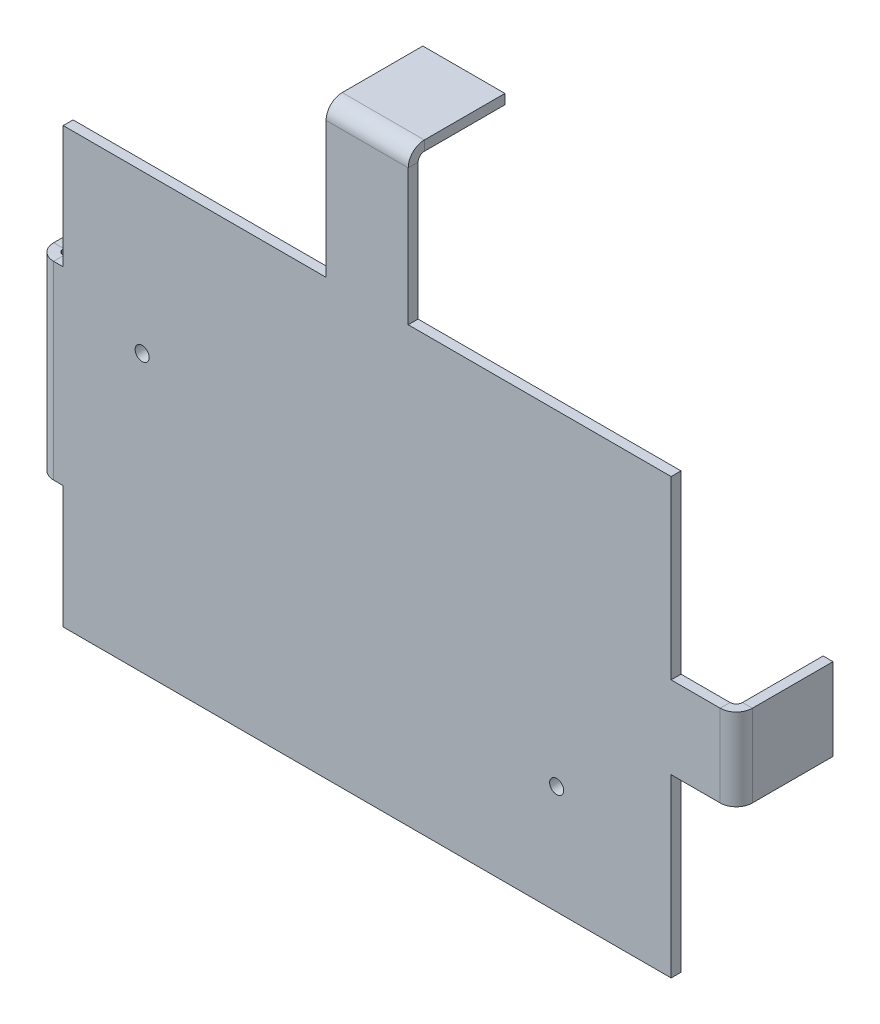
SolidWorks part; units mm, degrees
note: The reader was unsure of these and kept them because the rebuilt part matched: flange length of "Edge-Flange1".
ref_plane "Front Plane" through (0, 0, 0) normal (0, 0, 1) x (1, 0, 0)
ref_plane "Top Plane" through (0, 0, 0) normal (0, 1, 0) x (1, 0, 0)
ref_plane "Right Plane" through (0, 0, 0) normal (1, 0, 0) x (0, 0, -1)
sketch "Sketch4" plane through (0, 0, -2116.6331) normal (0, 0, 1) x (1, 0, 0)
  line L0 (69.2384, 17.8777) -> (69.2384, 4.6697)
  line L1 (69.2384, 4.6697) -> (60.3484, 4.6697)
  line L3 (60.3484, 4.6697) -> (60.3484, -23.6513)
  line L4 (60.3484, -23.6513) -> (-37.4416, -23.6513)
  line L5 (-37.4416, -23.6513) -> (-37.4416, -3.9663)
  line L7 (-37.4416, -3.9663) -> (-39.9816, -3.9663)
  line L8 (-39.9816, -3.9663) -> (-39.9816, 26.5137)
  line L9 (-39.9816, 26.5137) -> (-37.4416, 26.5137)
  line L10 (-37.4416, 26.5137) -> (-37.4416, 46.1987)
  line L11 (-37.4416, 46.1987) -> (4.8494, 46.1987)
  line L13 (4.8494, 46.1987) -> (4.8494, 69.0587)
  line L14 (4.8494, 69.0587) -> (18.0574, 69.0587)
  line L15 (18.0574, 69.0587) -> (18.0574, 46.1987)
  line L16 (18.0574, 46.1987) -> (60.3484, 46.1987)
  line L17 (60.3484, 46.1987) -> (60.3484, 17.8777)
  line L18 (60.3484, 17.8777) -> (69.2384, 17.8777)
  dimension "D1" = 30.48
  dimension "D2" = 13.208
  dimension "D3" = 13.208
  dimension "D4" = 22.86
  dimension "D5" = 8.89
  dimension "D6" = 97.79
  dimension "D7" = 42.291
  dimension "D8" = 2.54
sheet metal parameters "Sheet-Metal1" thickness 1.5875 parameters "D1"=1
base flange "Base-Flange1" sketch "Sketch4" thickness 1.5875 reverse thickness direction yes parameters "D1"=1
edge flange "Edge-Flange1" sketch "Sketch12" flange profiles "Sketch12", "Sketch13", "Sketch14" flange angle 90 flange length 13.97 flange position material outside bend radius 1 thickness 1.5875 relief rectangular parameters "D6"=10, "D8"=0.254
sketch "Sketch12" plane through (-39.9816, 0, -2116.6331) normal (-1, 0, 0) x (0, 1, 0)
  line L2 (-3.9663, 0) -> (-3.9663, 13.97)
  line L3 (-3.9663, 13.97) -> (26.5137, 13.97)
  line L4 (26.5137, 13.97) -> (26.5137, 0)
  line L5 (26.5137, 0) -> (-3.9663, 0) construction
  line L6 (26.5137, 0) -> (-3.9663, 0)
sketch "Sketch13" plane through (0, 69.0587, -2116.6331) normal (0, 1, 0) x (1, 0, 0)
  line L2 (4.8494, 0) -> (4.8494, 13.97)
  line L3 (4.8494, 13.97) -> (18.0574, 13.97)
  line L4 (18.0574, 13.97) -> (18.0574, 0)
  line L5 (18.0574, 0) -> (4.8494, 0) construction
  line L6 (18.0574, 0) -> (4.8494, 0)
sketch "Sketch14" plane through (69.2384, 0, -2116.6331) normal (1, 0, 0) x (0, -1, 0)
  line L2 (-17.8777, 0) -> (-17.8777, 13.97)
  line L3 (-17.8777, 13.97) -> (-4.6697, 13.97)
  line L4 (-4.6697, 13.97) -> (-4.6697, 0)
  line L5 (-4.6697, 0) -> (-17.8777, 0) construction
  line L6 (-4.6697, 0) -> (-17.8777, 0)
bend "EdgeBend1" bend radius 1 bend angle 90 parameters "D5"=1
bend "EdgeBend2" bend radius 1 bend angle 90 parameters "D5"=2
bend "EdgeBend3" bend radius 1 bend angle 90 parameters "D5"=3
hole_wizard "#4-40 Tapped Hole2" positions "3DSketch2" profile "Sketch18" tap size "#4-40" standard "Ansi Inch"
sketch3d "3DSketch2"
  line L0 (-37.4416, -23.6513, -2115.0456) -> (60.3484, -23.6513, -2115.0456) construction
  line L1 (-37.4416, 46.1987, -2115.0456) -> (-37.4416, 26.5137, -2115.0456) construction
  line L2 (60.3484, -23.6513, -2115.0456) -> (60.3484, 4.6697, -2115.0456) construction
  point P0 (41.9334, -6.1888, -2115.0456)
  point P2 (-24.7416, 20.7987, -2115.0456)
  dimension "D1" = 44.45
  dimension "D2" = 12.7
  dimension "D3" = 18.415
  dimension "D4" = 17.4625
sketch "Sketch18" plane through (41.9334, -6.1888, -2115.0456) normal (1, 0, 0) x (0, -1, 0)
  line L0 (0, 0) -> (0, 8.2992)
  line L1 (0, 8.2992) -> (1.1303, 7.62)
  line L2 (1.1303, 7.62) -> (1.1303, 0)
  line L5 (1.1303, 0) -> (0, 0)
  line L10 (0, 8.2992) -> (-1.1303, 7.62) construction
  line L11 (0, -6.35) -> (0, 107.95) construction
  dimension "Tap Drill Dia." = 2.2606
  dimension "Tap Drill Depth" = 7.62
  dimension "Drill Angle" = 118
cosmetic thread "Hole Thread5" parameters "D1"=5.588, "D2"=2.8448
cosmetic thread "Hole Thread6" parameters "D1"=5.588, "D2"=2.8448
flat pattern "Flat-Pattern1" [suppressed]
sketch "Bend-Lines1" plane through (0, 0, 1.5875) normal (0, 0, 1) x (1, 0, 0)
  line L0 (70.4733, 29.4273) -> (70.4733, -6.8799) construction
  line L1 (-4.9383, 70.198) -> (27.7667, 70.198) construction
  line L2 (-48.6414, -4.1577) -> (-48.6414, 26.7051) construction
  line L3 (70.4733, 29.4273) -> (70.4733, -6.8799) construction
  line L4 (-4.9383, 70.198) -> (27.7667, 70.198) construction
  line L5 (-48.6414, -4.1577) -> (-48.6414, 26.7051) construction
bend of the flat pattern "Flatten-<EdgeBend1>1"
bend of the flat pattern "Flatten-<EdgeBend2>1"
bend of the flat pattern "Flatten-<EdgeBend3>1"
